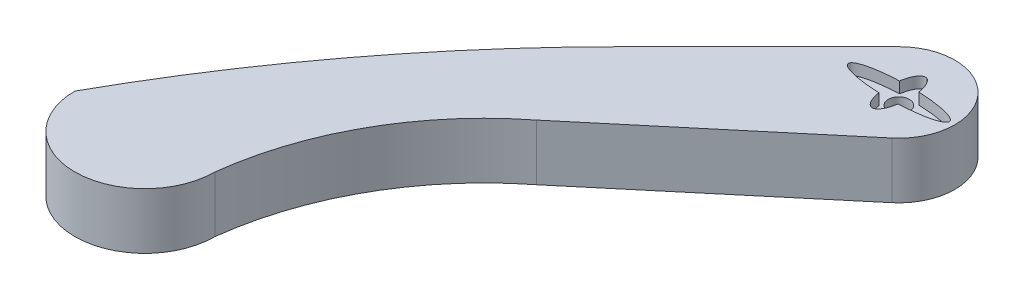
SolidWorks part; units mm, degrees
ref_plane "前视基准面" through (0, 0, 0) normal (0, 0, 1) x (1, 0, 0)
ref_plane "上视基准面" through (0, 0, 0) normal (0, 1, 0) x (1, 0, 0)
ref_plane "右视基准面" through (0, 0, 0) normal (1, 0, 0) x (0, 0, -1)
sketch "草图1" plane through (0, 0, 0) normal (0, 1, 0) x (1, 0, 0)
  line L0 (-14.1421, 14.1421) -> (-63.6396, -35.3553)
  line L1 (12.8558, -15.3209) -> (-56.0882, -73.1718)
  line L3 (-63.6396, -35.3553) -> (-56.0882, -73.1718) construction
  arc A0 (12.8558, -15.3209) -> (-14.1421, 14.1421) centre (0, 0) ccw
  arc A1 (-147.4785, -146.6526) -> (-97.4785, -146.6526) centre (-122.4785, -146.6526) ccw
  arc A2 (-56.0882, -73.1718) -> (-97.4785, -146.6526) centre (11.7362, -159.7734) ccw
  arc A3 (-63.6396, -35.3553) -> (-147.4785, -146.6526) centre (289.9138, -388.9087) ccw
  dimension "D1" = 40
  dimension "D2" = 50
  dimension "D5" = 110
  dimension "D6" = 500
  dimension "D3" = 90
  dimension "D4" = 70
  dimension "D7" = 146.6526
extrude "凸台-拉伸1" add sketch "草图1" along normal mid plane 20 contours A3 A1 A2 L1 A0 L0
ref_plane "基准面1" through (0, 10, 0) normal (0, -1, 0) x (-1, 0, 0)
sketch "草图2" plane through (0, 10, 0) normal (0, -1, 0) x (-1, 0, 0)
  circle A0 centre (0, 0) radius 3.75
sketch "草图3" plane through (0, 10, 0) normal (0, -1, 0) x (-1, 0, 0)
  line L0 (0, 0) -> (18, 0) construction
  line L1 (0, 0) -> (0, 9.5) construction
  ellipse E0 centre (0, 0) end of major axis (18, 0) minor radius 3.75 (-3.4572, 3.6802) -> (-3.4572, -3.6802) ccw
  ellipse E1 centre (0, 0) end of major axis (0, 9.5) minor radius 3.75 (-3.4572, -3.6802) -> (3.4572, -3.6802) ccw
  ellipse E2 centre (0, 0) end of major axis (0, 9.5) minor radius 3.75 (3.4572, 3.6802) -> (-3.4572, 3.6802) ccw
  ellipse E3 centre (0, 0) end of major axis (18, 0) minor radius 3.75 (3.4572, -3.6802) -> (3.4572, 3.6802) ccw
extrude "切除-拉伸2" cut sketch "草图2" against normal through all and the other way through all
extrude "切除-拉伸3" cut sketch "草图3" against normal blind 4 and the other way blind 4
